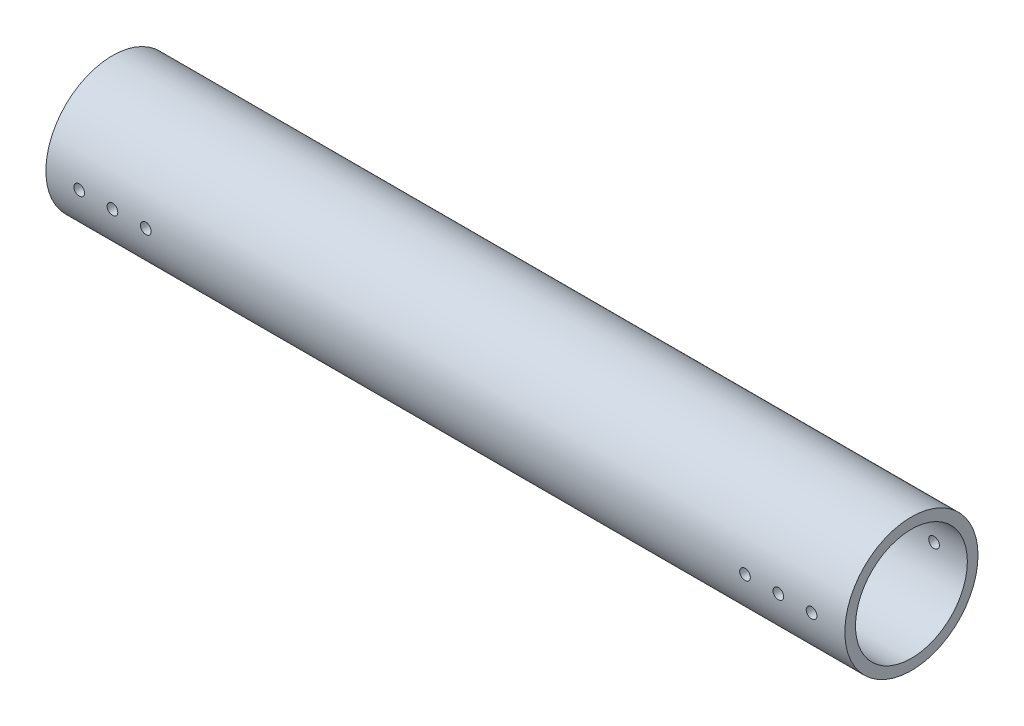
SolidWorks part; units mm, degrees
material "Zoltek Panex 33"
ref_plane "Спереди" through (0, 0, 0) normal (0, 0, 1) x (1, 0, 0)
ref_plane "Сверху" through (0, 0, 0) normal (0, 1, 0) x (1, 0, 0)
ref_plane "Справа" through (0, 0, 0) normal (1, 0, 0) x (0, 0, -1)
other "Configuration Table"
sketch "Эскиз2" plane through (0, 0, 0) normal (1, 0, 0) x (0, 0, -1)
  circle A0 centre (0, 0) radius 25
  circle A1 centre (0, 0) radius 21
  dimension "D1" = 50
  dimension "D2" = 42
extrude "Бобышка-Вытянуть2" add sketch "Эскиз2" along normal blind 300
ref_plane "Плоскость1" through (0, 0, 25) normal (0, 0, 1) x (1, 0, 0)
sketch "Эскиз4" plane through (0, 0, 25) normal (0, 0, 1) x (1, 0, 0)
  line L0 (0, -25) -> (300, -25) construction
  line L1 (300, -25) -> (300, 25) construction
  circle A0 centre (12.5, 0) radius 2
  circle A1 centre (287.5, 0) radius 2
  circle A2 centre (25, 0) radius 2
  circle A3 centre (37.5, 0) radius 2
  circle A4 centre (275, 0) radius 2
  circle A5 centre (262.5, 0) radius 2
  dimension "D1" = 4
  dimension "D4" = 4
  dimension "D6" = 4
  dimension "D8" = 4
  dimension "D10" = 4
  dimension "D11" = 4
  dimension "D2" = 12.5
  dimension "D3" = 25
  dimension "D5" = 12.5
  dimension "D7" = 12.5
  dimension "D9" = 12.5
  dimension "15" = 12.5
  dimension "D12" = 12.5
extrude "Вырез-Вытянуть2" cut sketch "Эскиз4" against normal through all and the other way blind 10 contours A0 | A1 | A2 | A3 | A5 | A4
equation "\"Diameter\"= 50мм"
equation "\"D1@Эскиз2\"= \"Diameter\""
equation "\"Length\" = 300мм"
equation "\"Thickness\"= 4мм"
equation "\"D1@Бобышка-Вытянуть2\"= \"Length\""
equation "\"D2@Эскиз2\" = \"Diameter\" - \"Thickness\" * 2"
equation "\"D4@Эскиз4\"=\"D1@Эскиз4\""
equation "\"D5@Эскиз4\"=\"D2@Эскиз4\""
equation "\"D3@Эскиз4\"=\"Diameter\"/2"
equation "\"D6@Эскиз4\"=\"D1@Эскиз4\""
equation "\"D8@Эскиз4\"=\"D6@Эскиз4\""
equation "\"D10@Эскиз4\"=\"D4@Эскиз4\""
equation "\"D11@Эскиз4\"=\"D4@Эскиз4\""
equation "\"D9@Эскиз4\"=\"D7@Эскиз4\""
